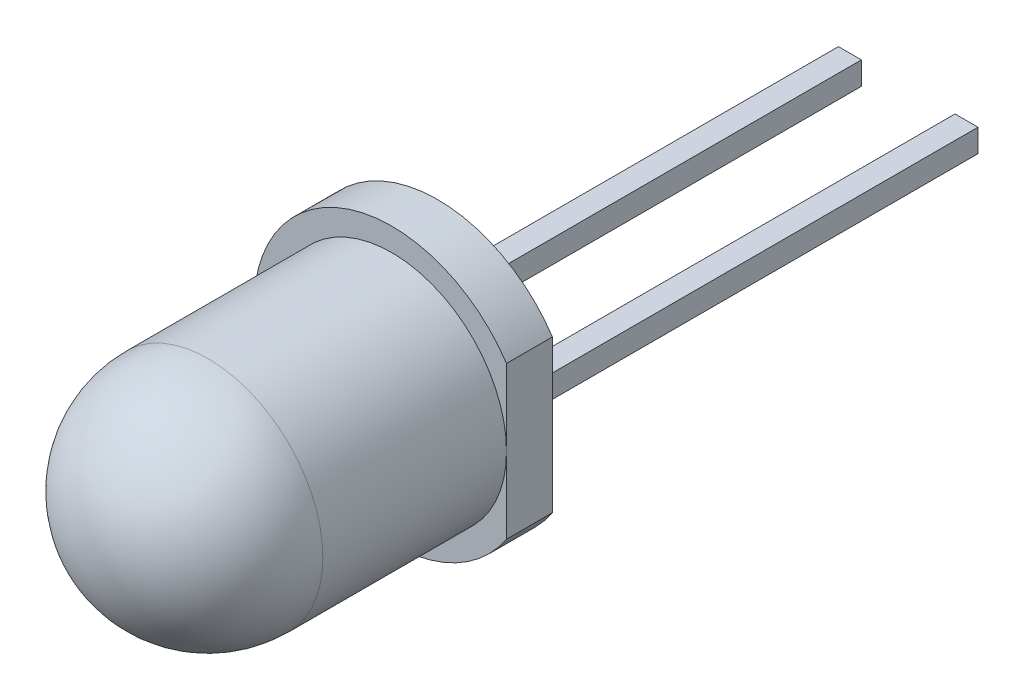
SolidWorks part; units mm, degrees
ref_plane "Front Plane" through (0, 0, 0) normal (0, 0, 1) x (1, 0, 0)
ref_plane "Top Plane" through (0, 0, 0) normal (0, 1, 0) x (1, 0, 0)
ref_plane "Right Plane" through (0, 0, 0) normal (1, 0, 0) x (0, 0, -1)
sketch "Sketch1" plane through (0, 0, 0) normal (0, 0, 1) x (1, 0, 0)
  circle A0 centre (0, 0) radius 3
  dimension "D1" = 6
extrude "Boss-Extrude1" add sketch "Sketch1" along normal blind 1
sketch "Sketch2" plane through (0, 0, 1) normal (0, 0, 1) x (1, 0, 0)
  circle A0 centre (0, 0) radius 2.5
  dimension "D1" = 5
extrude "Boss-Extrude2" add sketch "Sketch2" along normal blind 4
dome "Dome1" faces to dome 1 distance 2.5 reverse direction no elliptical dome no face at (2.5, 0, 5) parameters "D1"=2.5
sketch "Sketch3" plane through (0, 0, 1) normal (0, 0, 1) x (1, 0, 0)
  line L1 (2.5, 1.8503) -> (3, 1.8503)
  line L2 (2.5, 1.8503) -> (2.5, -2.181)
  line L3 (2.5, -2.181) -> (3, -2.181)
  line L4 (3, 1.8503) -> (3, -2.181)
  circle A0 centre (0, 0) radius 3 construction
  circle A1 centre (0, 0) radius 2.5 construction
extrude "Cut-Extrude1" cut sketch "Sketch3" against normal up to next normal cut yes
ref_plane "Plane3" through (0, 0, 0) normal (0, 1, 0) x (1, 0, 0)
sketch "Sketch8" plane through (0, 0, 0) normal (0, 1, 0) x (1, 0, 0)
  line L0 (0, 0) -> (-1.27, 0) construction
  line L1 (2.5, 0) -> (-3, 0) construction
  line L2 (-1.27, 0) -> (-1.27, 10)
  dimension "D1" = 10
  dimension "D2" = 1.27
sheet metal parameters "Sheet-Metal1" thickness 0.5 parameters "D1"=0.1
base flange "Base-Flange1" sketch "Sketch8" end condition mid plane depth 0.5 reverse direction no thickness 0.5 reverse thickness direction no bend radius 0.1
sketch "Sketch9" plane through (0, 0, 0) normal (0, 1, 0) x (1, 0, 0)
  line L0 (1.27, 0) -> (1.27, 10)
  line L1 (-1.27, 10) -> (-0.77, 10) construction
  line L2 (2.5, 0) -> (-3, 0) construction
  dimension "D1" = 1.27
sheet metal parameters "Sheet-Metal2" thickness 0.5 parameters "D1"=0.1
base flange "Base-Flange2" sketch "Sketch9" end condition mid plane depth 0.5 reverse direction no thickness 0.5 reverse thickness direction no bend radius 0.1
sketch "Sketch10" plane through (0, 0, 0) normal (0, 0, -1) x (-1, 0, 0)
  line L0 (0, 0) -> (0, 3) construction
  arc A0 (-2.5, -1.6583) -> (-2.5, 1.6583) centre (0, 0) ccw construction
ref_plane "Plane4" through (0, 0, 0) normal (1, 0, 0) x (0, 0, -1)
flat pattern "Flat-Pattern1" [suppressed]
sketch "Bend-Lines1" plane through (0, 0, 0) normal (0, 1, 0) x (1, 0, 0)
sketch3d "Bounding-Box1" [suppressed]
  line L0 (0, 0.5, 0) -> (4.53, 0.5, 0) construction
  line L1 (0, 0, 0) -> (4.53, 0, 0) construction
  line L2 (0, 0.5, 0) -> (0, 0, 0) construction
  line L3 (4.53, 0.5, 0) -> (4.53, 0, 0) construction
flat pattern "Flat-Pattern2" [suppressed]
sketch "Bend-Lines2" plane through (0, 0, 0) normal (0, 1, 0) x (1, 0, 0)
sketch "Bounding-Box2" [suppressed] plane through (0, 0, 0) normal (0, 1, 0) x (1, 0, 0)
